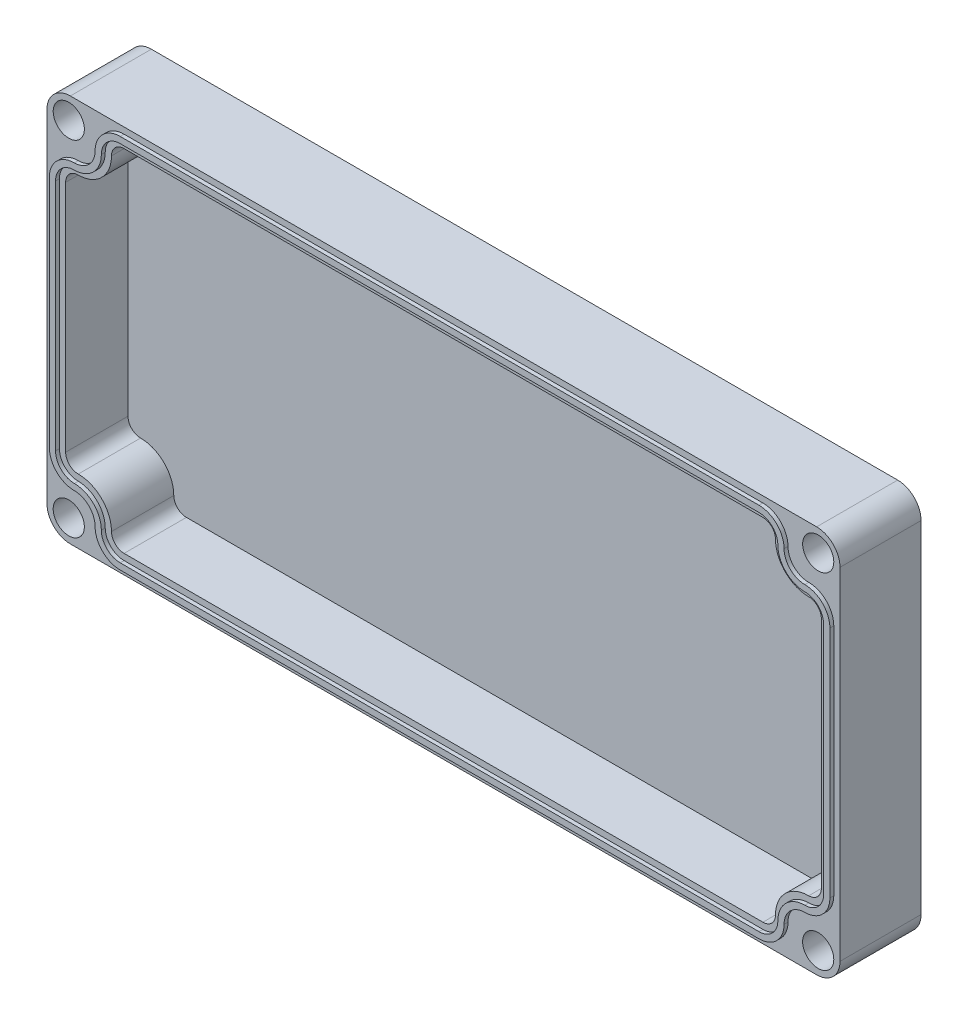
SolidWorks part; units mm, degrees
ref_plane "Plan de face" through (0, 0, 0) normal (0, 0, 1) x (1, 0, 0)
ref_plane "Plan de dessus" through (0, 0, 0) normal (0, 1, 0) x (1, 0, 0)
ref_plane "Plan de droite" through (0, 0, 0) normal (1, 0, 0) x (0, 0, -1)
sketch "Esquisse1" plane through (0, 0, 0) normal (0, 0, 1) x (1, 0, 0)
  line L1 (-48.5, 22.5) -> (48.5, 22.5)
  line L2 (-48.5, 22.5) -> (-48.5, -22.5)
  line L3 (-48.5, -22.5) -> (48.5, -22.5)
  line L4 (48.5, 22.5) -> (48.5, -22.5)
  line L5 (-48.5, 22.5) -> (48.5, -22.5) construction
  line L6 (-48.5, -22.5) -> (48.5, 22.5) construction
  point P0 (0, 0)
  dimension "D1" = 97
  dimension "D2" = 45
extrude "Boss.-Extru.1" add sketch "Esquisse1" along normal blind 8
shell "Coque1" thickness 2.4 removed face at (0, 0, 8) outward yes
ref_plane "Plan1" through (0, 0, 20) normal (0, 0, 1) x (1, 0, 0)
sketch "Esquisse10" plane through (0, 0, 0) normal (0, 0, 1) x (1, 0, 0)
  line L0 (-48.5, 22.5) -> (-48.5, 15)
  line L1 (-48.5, 22.5) -> (-48.5, -22.5) construction
  line L2 (48.5, 22.5) -> (-48.5, 22.5) construction
  line L3 (-41, 22.5) -> (-48.5, 22.5)
  line L4 (-46.88, 15) -> (-48.5, 15) construction
  line L5 (-46.88, 15) -> (-46.88, 16.62) construction
  line L6 (-41, 20.88) -> (-42.62, 20.88) construction
  line L7 (-41, 20.88) -> (-41, 22.5) construction
  arc A1 (-48.5, 15) -> (-46.88, 16.62) centre (-46.88, 15) cw
  arc A2 (-46.88, 16.62) -> (-42.62, 20.88) centre (-46.88, 20.88) ccw
  arc A3 (-42.62, 20.88) -> (-41, 22.5) centre (-41, 20.88) cw
  dimension "D1" = 7.5
extrude "Boss.-Extru.2" add sketch "Esquisse10" along normal up to surface (8 mm away) up to face at (0, 0, 8)
mirror "Symétrie1" about plane through (0, 0, 0) normal (1, 0, 0) of "Boss.-Extru.2"
mirror "Symétrie2" about plane through (0, 0, 0) normal (0, 1, 0) of "Boss.-Extru.2"
mirror "Symétrie3" about plane through (0, 0, 0) normal (0, 1, 0) of "Symétrie1"
sketch "Esquisse13" plane through (0, 0, 8) normal (0, 0, 1) x (1, 0, 0)
  line L0 (-48.1, 22.1) -> (-48.1, 24.1) construction
  line L1 (50.9, 24.9) -> (-50.9, 24.9) construction
  line L2 (-48.1, 22.1) -> (-50.1, 22.1) construction
  line L4 (-50.9, 24.9) -> (-50.9, -24.9) construction
  circle A0 centre (-48.1, 22.1) radius 2
  circle A1 centre (-48.1, 22.1) radius 2.75 construction
  dimension "D1" = 4
  dimension "D4" = 5.5
  dimension "D2" = 0.8
  dimension "D3" = 0.8
extrude "Insert" cut sketch "Esquisse13" against normal up to next
mirror "Symétrie4" about plane through (0, 0, 0) normal (1, 0, 0) of "Insert"
mirror "Symétrie5" about plane through (0, 0, 0) normal (0, 1, 0) of "Symétrie4"
sketch "Esquisse14" plane through (0, 0, 8) normal (0, 0, 1) x (1, 0, 0)
  line L0 (-41, 22.5) -> (41, 22.5) construction
  line L1 (48.5, 15) -> (48.5, -15) construction
  line L2 (41, -22.5) -> (-41, -22.5) construction
  line L3 (-48.5, -15) -> (-48.5, 15) construction
  line L4 (-50.1, -15) -> (-50.1, 15) construction
  line L5 (-41, 24.1) -> (41, 24.1) construction
  line L6 (50.1, 15) -> (50.1, -15) construction
  line L7 (41, -24.1) -> (-41, -24.1) construction
  line L8 (-41, 23.3) -> (41, 23.3)
  line L9 (49.3, 15) -> (49.3, -15)
  line L10 (41, -23.3) -> (-41, -23.3)
  line L11 (-49.3, -15) -> (-49.3, 15)
  arc A0 (41, 22.5) -> (42.62, 20.88) centre (41, 20.88) cw construction
  arc A1 (42.62, 20.88) -> (46.88, 16.62) centre (46.88, 20.88) ccw construction
  arc A2 (46.88, 16.62) -> (48.5, 15) centre (46.88, 15) cw construction
  arc A3 (48.5, -15) -> (46.88, -16.62) centre (46.88, -15) cw construction
  arc A4 (46.88, -16.62) -> (42.62, -20.88) centre (46.88, -20.88) ccw construction
  arc A5 (42.62, -20.88) -> (41, -22.5) centre (41, -20.88) cw construction
  arc A6 (-41, -22.5) -> (-42.62, -20.88) centre (-41, -20.88) cw construction
  arc A7 (-42.62, -20.88) -> (-46.88, -16.62) centre (-46.88, -20.88) ccw construction
  arc A8 (-46.88, -16.62) -> (-48.5, -15) centre (-46.88, -15) cw construction
  arc A9 (-48.5, 15) -> (-46.88, 16.62) centre (-46.88, 15) cw construction
  arc A10 (-46.88, 16.62) -> (-42.62, 20.88) centre (-46.88, 20.88) ccw construction
  arc A11 (-42.62, 20.88) -> (-41, 22.5) centre (-41, 20.88) cw construction
  arc A12 (-50.1, 15) -> (-46.88, 18.22) centre (-46.88, 15) cw construction
  arc A13 (-46.88, 18.22) -> (-44.22, 20.88) centre (-46.88, 20.88) ccw construction
  arc A14 (-44.22, 20.88) -> (-41, 24.1) centre (-41, 20.88) cw construction
  arc A15 (41, 24.1) -> (44.22, 20.88) centre (41, 20.88) cw construction
  arc A16 (44.22, 20.88) -> (46.88, 18.22) centre (46.88, 20.88) ccw construction
  arc A17 (46.88, 18.22) -> (50.1, 15) centre (46.88, 15) cw construction
  arc A18 (50.1, -15) -> (46.88, -18.22) centre (46.88, -15) cw construction
  arc A19 (46.88, -18.22) -> (44.22, -20.88) centre (46.88, -20.88) ccw construction
  arc A20 (44.22, -20.88) -> (41, -24.1) centre (41, -20.88) cw construction
  arc A21 (-41, -24.1) -> (-44.22, -20.88) centre (-41, -20.88) cw construction
  arc A22 (-44.22, -20.88) -> (-46.88, -18.22) centre (-46.88, -20.88) ccw construction
  arc A23 (-46.88, -18.22) -> (-50.1, -15) centre (-46.88, -15) cw construction
  arc A24 (-43.42, 20.88) -> (-41, 23.3) centre (-41, 20.88) cw
  arc A25 (41, 23.3) -> (43.42, 20.88) centre (41, 20.88) cw
  arc A26 (43.42, 20.88) -> (46.88, 17.42) centre (46.88, 20.88) ccw
  arc A27 (46.88, 17.42) -> (49.3, 15) centre (46.88, 15) cw
  arc A28 (49.3, -15) -> (46.88, -17.42) centre (46.88, -15) cw
  arc A29 (46.88, -17.42) -> (43.42, -20.88) centre (46.88, -20.88) ccw
  arc A30 (43.42, -20.88) -> (41, -23.3) centre (41, -20.88) cw
  arc A31 (-41, -23.3) -> (-43.42, -20.88) centre (-41, -20.88) cw
  arc A32 (-43.42, -20.88) -> (-46.88, -17.42) centre (-46.88, -20.88) ccw
  arc A33 (-46.88, -17.42) -> (-49.3, -15) centre (-46.88, -15) cw
  arc A34 (-49.3, 15) -> (-46.88, 17.42) centre (-46.88, 15) cw
  arc A35 (-46.88, 17.42) -> (-43.42, 20.88) centre (-46.88, 20.88) ccw
  dimension "D1" = 1.6
  dimension "D2" = 0.8
extrude "Extru.-Mince1" add sketch "Esquisse14" along normal blind 0.5 thin thin type one direction wall 0.8
fillet "Congé1" radius 3 4 edges at (-50.9, -24.9, 2.8) (50.9, -24.9, 2.8) (50.9, 24.9, 2.8) (-50.9, 24.9, 2.8)
sketch "Esquisse15" plane through (0, 0, -2.4) normal (0, 0, -1) x (-1, 0, 0)
  line L0 (36.5677, 119.0943) -> (94.262, 119.0943) construction
  line L1 (52.6667, 130) -> (263.3333, 130) construction
equation "\"buse\"= 0.8"
equation "\"D1@Coque1\"=\"buse\"*3"
equation "\"hauteur\"=10"
equation "\"D1@Nervure1\"=\"hauteur\""
equation "\"D1@Nervure18\"=\"buse\""
equation "\"D2@Esquisse13\"=\"buse\"*1"
equation "\"D3@Esquisse13\"=1*\"buse\""
